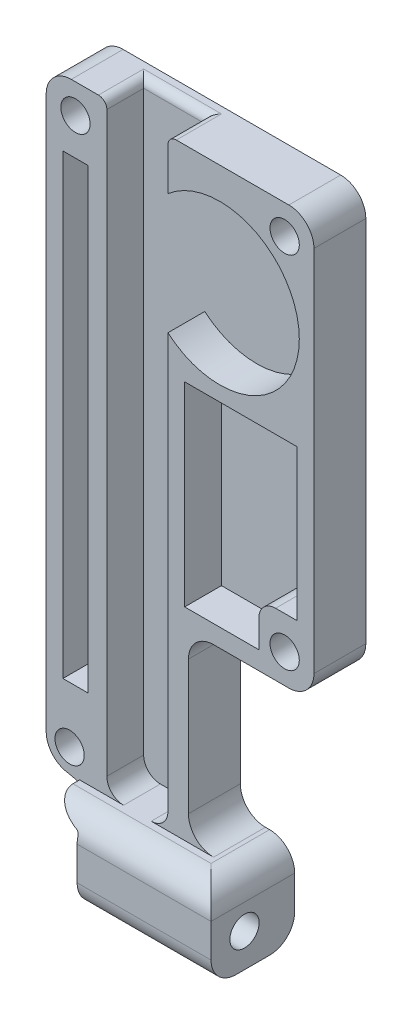
SolidWorks part; units mm, degrees
ref_plane "Ebene vorne" through (0, 0, 0) normal (0, 0, 1) x (1, 0, 0)
ref_plane "Ebene oben" through (0, 0, 0) normal (0, 1, 0) x (1, 0, 0)
ref_plane "Ebene rechts" through (0, 0, 0) normal (1, 0, 0) x (0, 0, -1)
sketch "body_sketch" plane through (0, 0, 0) normal (0, 0, 1) x (1, 0, 0)
  line L0 (0, 0) -> (0, 41.1005) construction
  line L1 (0, 41.1005) -> (0, -48.5733) construction
  line L2 (0, -35.6442) -> (0, 36.3558)
  line L3 (0, 36.3558) -> (32, 36.3558)
  line L4 (32, 36.3558) -> (32, -13.6442)
  line L5 (32, -13.6442) -> (17, -13.6442)
  line L6 (17, -13.6442) -> (17, -35.6442)
  line L7 (17, -35.6442) -> (0, -35.6442)
  dimension "D1" = 72
  dimension "D2" = 32
  dimension "D3" = 50
  dimension "D4" = 17
extrude "body" add sketch "body_sketch" along normal mid plane 6.2
sketch "channel" plane through (0, 0, 3.1) normal (0, 0, 1) x (1, 0, 0)
  line L0 (10.9, 36.3558) -> (10.9, -35.6442) construction
  line L1 (32, 36.3558) -> (0, 36.3558) construction
  line L2 (0, -35.6442) -> (17, -35.6442) construction
  line L3 (17, -35.6442) -> (17, -13.6442) construction
  line L5 (7.25, 36.3558) -> (14.55, 36.3558)
  line L6 (7.25, 36.3558) -> (7.25, -35.6442)
  line L7 (7.25, -35.6442) -> (14.55, -35.6442)
  line L8 (14.55, 36.3558) -> (14.55, -35.6442)
  line L9 (7.25, 36.3558) -> (14.55, -35.6442) construction
  line L10 (7.25, -35.6442) -> (14.55, 36.3558) construction
  point P8 (10.9, 0.3558)
  dimension "D1" = 6.1
  dimension "D2" = 7.3
extrude "pigionchannel" cut sketch "channel" against normal blind 4.4
sketch "Skizze2" plane through (0, 0, 3.1) normal (0, 0, 1) x (1, 0, 0)
  line L0 (7.25, 36.3558) -> (0, 36.3558) construction
  line L1 (0, 36.3558) -> (0, -35.6442) construction
  line L2 (32, 36.3558) -> (14.55, 36.3558) construction
  line L3 (32, -13.6442) -> (32, 36.3558) construction
  line L4 (17, -13.6442) -> (32, -13.6442) construction
  line L5 (0, -35.6442) -> (7.25, -35.6442) construction
  circle A0 centre (3.5, 32.8558) radius 1.75
  circle A1 centre (28.5, 32.8558) radius 1.75
  circle A2 centre (28.5, -10.1442) radius 1.75
  circle A3 centre (2.8, -32.8442) radius 1.75
  dimension "D1" = 3.5
  dimension "D5" = 3.5
  dimension "D6" = 3.5
  dimension "D8" = 3.5
  dimension "D2" = 3.5
  dimension "D3" = 3.5
  dimension "D4" = 3.5
  dimension "D7" = 3.5
  dimension "D9" = 2.8
  dimension "D10" = 2.8
extrude "screws" cut sketch "Skizze2" against normal through all
fillet "Verrundung1" radius 3 2 edges at (0, 36.3558, 0) (32, 36.3558, 0)
fillet "Verrundung2" radius 1 3 edges at (7.25, 36.3558, 0.9) (14.55, 36.3558, 0.9) (10.9, 36.3558, -1.3)
fillet "Verrundung3" radius 3 1 edges at (32, -13.6442, 0)
sketch "Skizze6" plane through (0, -35.6442, 0) normal (0, -1, 0) x (1, 0, 0)
  line L0 (0, -3.1) -> (17, -3.1) construction
  line L1 (4, -3.1) -> (23.5, -3.1)
  line L2 (4, -3.1) -> (4, 6.9)
  line L3 (4, 6.9) -> (23.5, 6.9)
  line L4 (23.5, -3.1) -> (23.5, 6.9)
  line L5 (0, 3.1) -> (0, -3.1) construction
  dimension "D1" = 19.5
  dimension "D2" = 10
  dimension "D3" = 4
extrude "handle" add sketch "Skizze6" along normal blind 10
sketch "Skizze7" plane through (23.5, 0, 0) normal (1, 0, 0) x (0, 0, -1)
  line L0 (3.1, -45.6442) -> (-6.9, -45.6442) construction
  line L1 (-6.9, -45.6442) -> (-6.9, -35.6442) construction
  circle A0 centre (-2.9, -41.6442) radius 1.75
  dimension "D1" = 3.5
  dimension "D2" = 4
  dimension "D3" = 4
extrude "Schnitt-Linear austragen3" cut sketch "Skizze7" against normal through all
sketch "Skizze8" plane through (4, 0, 0) normal (-1, 0, 0) x (0, 0, 1)
  line L0 (6.9, -45.6442) -> (6.9, -35.6442) construction
  line L1 (6.9, -37.3701) -> (-3.1, -37.3701)
  line L2 (6.9, -37.3701) -> (6.9, -45.6442)
  line L3 (6.9, -45.6442) -> (-3.1, -45.6442)
  line L4 (-3.1, -37.3701) -> (-3.1, -45.6442)
  line L5 (6.9, -45.6442) -> (-3.1, -45.6442) construction
extrude "Schnitt-Linear austragen4" cut sketch "Skizze8" against normal blind 3.5
fillet "Verrundung7" radius 3 1 edges at (15.5, -45.6442, 6.9)
fillet "Verrundung8" radius 3 1 edges at (15.5, -45.6442, -3.1)
fillet "Verrundung12" radius 3 1 edges at (17, -13.6442, 0)
fillet "Verrundung13" radius 3 1 edges
fillet "Verrundung14" radius 3 1 edges at (0, -35.6442, 0)
fillet "Verrundung16" radius 2 2 edges at (14.55, -35.6442, 0.9) (7.25, -35.6442, 0.9)
sketch "Skizze9" plane through (0, 0, 3.1) normal (0, 0, 1) x (1, 0, 0)
  line L0 (29, 36.3558) -> (15.55, 36.3558) construction
  line L1 (32, -10.6442) -> (32, 33.3558) construction
  circle A0 centre (20.75, 23.1058) radius 9.5
  dimension "D1" = 19
  dimension "D2" = 13.25
  dimension "D3" = 11.25
extrude "gear cage" cut sketch "Skizze9" against normal blind 4.4
sketch "Skizze10" plane through (0, 0, 3.1) normal (0, 0, 1) x (1, 0, 0)
  line L0 (32, -10.6442) -> (32, 33.3558) construction
  line L1 (16.55, 11.8313) -> (30, 11.8313)
  line L2 (16.55, 11.8313) -> (16.55, -11.466)
  line L3 (16.55, -11.466) -> (25.4181, -11.466)
  line L4 (30, 11.8313) -> (30, -6.1687)
  line L5 (14.55, -33.6442) -> (14.55, 15.9079) construction
  line L6 (25.4181, -11.466) -> (25.4181, -6.1687)
  line L7 (25.4181, -6.1687) -> (30, -6.1687)
  dimension "D1" = 2
  dimension "D2" = 2
  dimension "D3" = 18
extrude "Schnitt-Linear austragen6" cut sketch "Skizze10" against normal blind 4.4
fillet "Verrundung17" radius 2 1 edges at (25.4181, -6.1687, 0.9)
sketch "Skizze11" plane through (0, 0, 3.1) normal (0, 0, 1) x (1, 0, 0)
  line L0 (3.5, 32.8558) -> (3.5, -30.5574) construction
  line L1 (0, 33.3558) -> (0, -32.6442) construction
  line L3 (2, 28.4481) -> (5, 28.4481)
  line L4 (2, 28.4481) -> (2, -26.1496)
  line L5 (2, -26.1496) -> (5, -26.1496)
  line L6 (5, 28.4481) -> (5, -26.1496)
  line L7 (2, 28.4481) -> (5, -26.1496) construction
  line L8 (2, -26.1496) -> (5, 28.4481) construction
  point P7 (3.5, 1.1492)
  dimension "D1" = 2
extrude "Schnitt-Linear austragen7" cut sketch "Skizze11" against normal blind 4.4
fillet "Verrundung18" radius 3 2 edges at (13.75, -35.6442, 6.9) (23.5, -35.6442, 1.9)
fillet "Verrundung19" radius 0.5 1 edges at (7.5, -37.3701, 1.758)
fillet "Verrundung20" radius 10 1 edges at (4, -37.3701, 1.758)
fillet "Verrundung22" radius 8 1 edges
